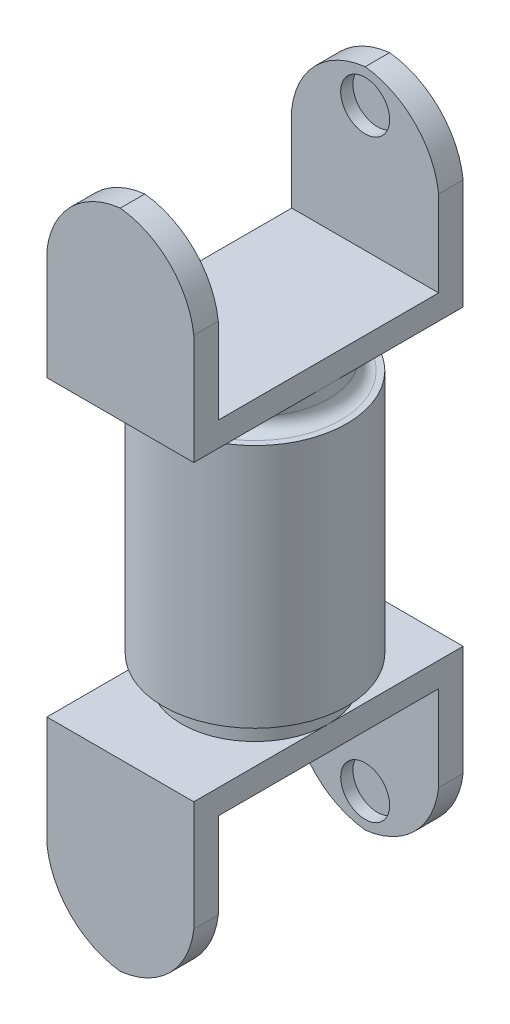
SolidWorks part; units mm, degrees
ref_plane "Front Plane" through (0, 0, 0) normal (0, 0, 1) x (1, 0, 0)
ref_plane "Top Plane" through (0, 0, 0) normal (0, 1, 0) x (1, 0, 0)
ref_plane "Right Plane" through (0, 0, 0) normal (1, 0, 0) x (0, 0, -1)
sketch "Sketch1" plane through (0, 0, 0) normal (0, 1, 0) x (1, 0, 0)
  circle A0 centre (0, 0) radius 7.5
  dimension "D1" = 15
extrude "Boss-Extrude1" add sketch "Sketch1" along normal blind 10
sketch "Sketch5" plane through (0, 10, 0) normal (0, 1, 0) x (1, 0, 0)
  circle A0 centre (0, 0) radius 6
  dimension "D1" = 12
extrude "Boss-Extrude2" add sketch "Sketch5" along normal blind 2
fillet "Fillet2" radius 1 1 edges at (0, 10, 6)
sketch "Sketch6" plane through (0, 0, 0) normal (1, 0, 0) x (0, 0, -1)
  line L0 (6, 12) -> (-6, 12) construction
  line L1 (6, 12) -> (-6, 12)
  line L2 (6, 12) -> (11, 12)
  line L3 (11, 12) -> (11, 27)
  line L4 (11, 27) -> (9, 27)
  line L5 (9, 27) -> (9, 14)
  line L6 (9, 14) -> (-9, 14)
  line L7 (-9, 14) -> (-9, 27)
  line L8 (-9, 27) -> (-11, 27)
  line L9 (-11, 27) -> (-11, 12)
  line L10 (-11, 12) -> (-6, 12)
  dimension "D1" = 15
  dimension "D2" = 2
  dimension "D3" = 13
  dimension "D4" = 5
extrude "Boss-Extrude3" add sketch "Sketch6" along normal blind 6 and the other way blind 6
sketch "Sketch9" plane through (0, 0, 11) normal (0, 0, 1) x (1, 0, 0)
  line L0 (0, 27) -> (0, 12) construction
  line L4 (-6, 12) -> (6, 12)
  line L5 (6, 12) -> (6, 27)
  line L6 (6, 27) -> (-6, 27)
  line L7 (-6, 27) -> (-6, 12)
  line L8 (-6, 12) -> (6, 12)
  line L9 (6, 12) -> (6, 27)
  line L10 (6, 27) -> (-6, 27)
  line L11 (-6, 27) -> (-6, 12)
  arc A0 (0, 27) -> (-6, 19.5) centre (0.75, 20.25) ccw
  arc A1 (0, 27) -> (6, 19.5) centre (-0.75, 20.25) cw
  line M7 (6, 12) -> (6, 27)
  line M8 (6, 27) -> (-6, 27)
  line M9 (-6, 27) -> (-6, 12)
  dimension "D1" = 0
extrude "Cut-Extrude4" cut sketch "Sketch9" against normal blind 29 contours A0 L10 M9 | A1 M8 M7 region at (-4.5286, 25.5286, 11) region at (4.5286, 25.5286, 11)
sketch "Sketch10" plane through (0, 0, 9) normal (0, 0, -1) x (-1, 0, 0)
  line L0 (6, 14) -> (6, 21) construction
  circle A0 centre (0, 24.25) radius 2
  arc A1 (6, 21) -> (0, 27) centre (-0.75, 20.25) ccw construction
  dimension "D1" = 4
  dimension "D2" = 4
  dimension "D3" = 6
extrude "Cut-Extrude5" cut sketch "Sketch10" against normal blind 1 and the other way blind 19
mirror "Mirror2" about plane through (0, 0, 0) normal (0, 1, 0) of "Boss-Extrude1"
mirror "Mirror9" about plane through (0, 0, 0) normal (0, 1, 0) of "Boss-Extrude3", "Boss-Extrude2"
mirror "Mirror11" about plane through (0, 0, 0) normal (0, 1, 0) of "Cut-Extrude5", "Cut-Extrude4"
